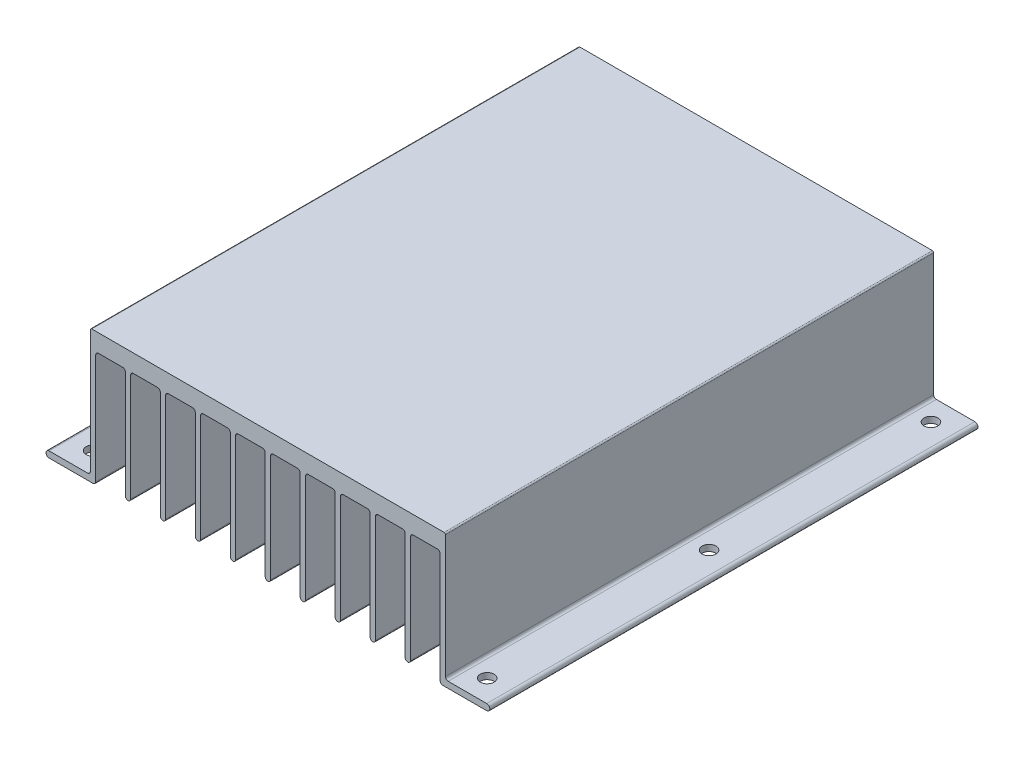
SolidWorks part; units mm, degrees
ref_plane "Front Plane" through (0, 0, 0) normal (0, 0, 1) x (1, 0, 0)
ref_plane "Top Plane" through (0, 0, 0) normal (0, 1, 0) x (1, 0, 0)
ref_plane "Right Plane" through (0, 0, 0) normal (1, 0, 0) x (0, 0, -1)
sketch "Sketch1" plane through (0, 0, 0) normal (0, 0, 1) x (1, 0, 0)
  line L0 (62.6108, -36.322) -> (50.8, -36.322)
  line L1 (50.8, -36.322) -> (50.8, 0)
  line L2 (50.8, 0) -> (-50.8, 0)
  line L3 (-50.8, 0) -> (-50.8, -36.322)
  line L4 (-50.8, -36.322) -> (-62.6108, -36.322)
  line L5 (-62.6108, -38.1005) -> (-49.276, -38.1005)
  line L6 (-49.276, -38.1005) -> (-49.276, -5.0805)
  line L7 (-49.276, -5.0805) -> (-40.7924, -5.0805)
  line L8 (-40.7924, -5.0805) -> (-40.7924, -36.5765)
  line L9 (-39.2684, -36.5765) -> (-39.2684, -5.0805)
  line L10 (-39.2684, -5.0805) -> (-30.7848, -5.0805)
  line L11 (-30.7848, -5.0805) -> (-30.7848, -36.5765)
  line L12 (-29.2608, -36.5765) -> (-29.2608, -5.0805)
  line L13 (-29.2608, -5.0805) -> (-20.7772, -5.0805)
  line L14 (-20.7772, -5.0805) -> (-20.7772, -36.5765)
  line L15 (-19.2532, -36.5765) -> (-19.2532, -5.0805)
  line L16 (-19.2532, -5.0805) -> (-10.7696, -5.0805)
  line L17 (-10.7696, -5.0805) -> (-10.7696, -36.5765)
  line L18 (-9.2456, -36.5765) -> (-9.2456, -5.0805)
  line L19 (-9.2456, -5.0805) -> (-0.762, -5.0805)
  line L20 (-0.762, -5.0805) -> (-0.762, -36.5765)
  line L21 (0.762, -36.5765) -> (0.762, -5.0805)
  line L22 (0.762, -5.0805) -> (9.2456, -5.0805)
  line L23 (9.2456, -5.0805) -> (9.2456, -36.5765)
  line L24 (10.7696, -36.5765) -> (10.7696, -5.0805)
  line L25 (10.7696, -5.0805) -> (19.2532, -5.0805)
  line L26 (19.2532, -5.0805) -> (19.2532, -36.5765)
  line L27 (20.7772, -36.5765) -> (20.7772, -5.0805)
  line L28 (20.7772, -5.0805) -> (29.2608, -5.0805)
  line L29 (29.2608, -5.0805) -> (29.2608, -36.5765)
  line L30 (30.7848, -36.5765) -> (30.7848, -5.0805)
  line L31 (30.7848, -5.0805) -> (39.2684, -5.0805)
  line L32 (39.2684, -5.0805) -> (39.2684, -36.5765)
  line L33 (40.7924, -36.5765) -> (40.7924, -5.0805)
  line L34 (40.7924, -5.0805) -> (49.276, -5.0805)
  line L35 (49.276, -5.0805) -> (49.276, -38.1005)
  line L36 (49.276, -38.1005) -> (62.6108, -38.1005)
  arc A0 (-62.6108, -36.322) -> (-62.6108, -38.1005) centre (-62.6108, -37.2112) ccw
  arc A1 (-40.7924, -36.5765) -> (-39.2684, -36.5765) centre (-40.0304, -36.5765) ccw
  arc A2 (-30.7848, -36.5765) -> (-29.2608, -36.5765) centre (-30.0228, -36.5765) ccw
  arc A3 (-20.7772, -36.5765) -> (-19.2532, -36.5765) centre (-20.0152, -36.5765) ccw
  arc A4 (-10.7696, -36.5765) -> (-9.2456, -36.5765) centre (-10.0076, -36.5765) ccw
  arc A5 (-0.762, -36.5765) -> (0.762, -36.5765) centre (0, -36.5765) ccw
  arc A6 (9.2456, -36.5765) -> (10.7696, -36.5765) centre (10.0076, -36.5765) ccw
  arc A7 (19.2532, -36.5765) -> (20.7772, -36.5765) centre (20.0152, -36.5765) ccw
  arc A8 (29.2608, -36.5765) -> (30.7848, -36.5765) centre (30.0228, -36.5765) ccw
  arc A9 (39.2684, -36.5765) -> (40.7924, -36.5765) centre (40.0304, -36.5765) ccw
  arc A10 (62.6108, -38.1005) -> (62.6108, -36.322) centre (62.6108, -37.2112) ccw
extrude "Boss-Extrude1" add sketch "Sketch1" against normal blind 139.7
hole_wizard "5/32 (0.15625) Diameter Hole1" positions "Sketch3" profile "Sketch2" hole size "5/32" standard "ANSI Inch"
sketch "Sketch3" plane through (0, -38.1005, 0) normal (0, -1, 0) x (-1, 0, 0)
  point P0 (56.388, 6.35)
  point P1 (56.388, 69.85)
  point P2 (56.388, 133.35)
  point P3 (-56.388, 6.35)
  point P4 (-56.388, 69.85)
  point P5 (-56.388, 133.35)
sketch "Sketch2" plane through (-56.388, -38.1005, -6.35) normal (1, 0, 0) x (0, 0, -1)
  line L0 (0, 0) -> (0, 38.1005)
  line L1 (0, 38.1005) -> (1.9844, 38.1005)
  line L2 (1.9844, 38.1005) -> (1.9844, 0)
  line L5 (1.9844, 0) -> (0, 0)
  line L11 (0, -6.35) -> (0, 107.95) construction
  dimension "Thru Hole Dia." = 3.9687
  dimension "Thru Hole Depth" = 38.1005
fillet "Fillet1" radius 0.381 2 edges at (-50.8, 0, -69.85) (50.8, 0, -69.85) tangent propagation no
fillet "Fillet2" radius 0.7874 24 edges at (20.7772, -5.0805, -69.85) (-50.8, -36.322, -69.85) (40.7924, -5.0805, -69.85) (-49.276, -5.0805, -69.85) (10.7696, -5.0805, -69.85) (-40.7924, -5.0805, -69.85) (30.7848, -5.0805, -69.85) (-39.2684, -5.0805, -69.85) (49.276, -38.1005, -69.85) (-30.7848, -5.0805, -69.85) (-49.276, -38.1005, -69.85) (-29.2608, -5.0805, -69.85) (19.2532, -5.0805, -69.85) (-20.7772, -5.0805, -69.85) (29.2608, -5.0805, -69.85) (-19.2532, -5.0805, -69.85) (39.2684, -5.0805, -69.85) (-10.7696, -5.0805, -69.85) (49.276, -5.0805, -69.85) (-9.2456, -5.0805, -69.85) (50.8, -36.322, -69.85) (-0.762, -5.0805, -69.85) (0.762, -5.0805, -69.85) (9.2456, -5.0805, -69.85) tangent propagation no
sketch "Sketch4" plane through (0, 0, 0) normal (0, 1, 0) x (1, 0, 0)
  line L0 (0, 139.7) -> (0, 0) construction
  line L1 (50.419, 139.7) -> (-50.419, 139.7) construction
  line L2 (0, 69.85) -> (15.902, 69.85) construction
  circle A0 centre (0, 69.85) radius 12.7
  dimension "D1" = 25.4
